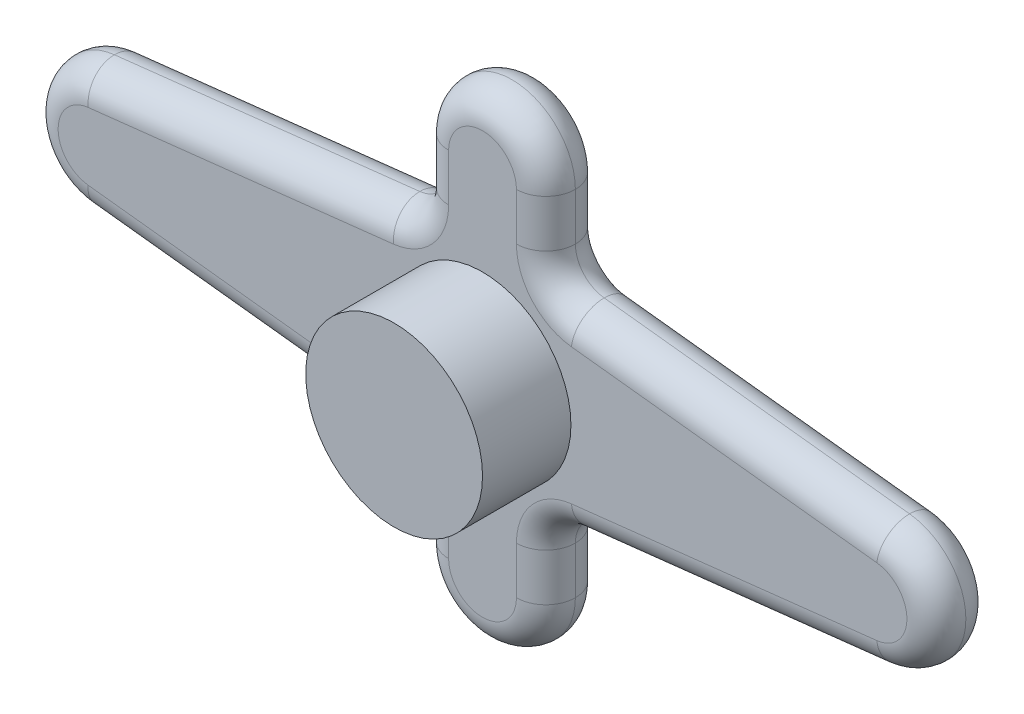
SolidWorks part; units mm, degrees
ref_plane "Front Plane" through (0, 0, 0) normal (0, 0, 1) x (1, 0, 0)
ref_plane "Top Plane" through (0, 0, 0) normal (0, 1, 0) x (1, 0, 0)
ref_plane "Right Plane" through (0, 0, 0) normal (1, 0, 0) x (0, 0, -1)
sketch "Sketch1" plane through (0, 0, 1307.6778) normal (0, 0, 1) x (1, 0, 0)
  line L16 (676.2339, 870.8041) -> (676.2339, 869.198)
  line L17 (680.5339, 869.198) -> (680.5339, 870.8041)
  line L18 (681.5111, 871.8972) -> (691.8739, 873.0615)
  line L19 (691.8739, 877.3346) -> (681.5111, 878.4989)
  line L20 (680.5339, 879.592) -> (680.5339, 881.198)
  line L21 (676.2339, 881.198) -> (676.2339, 879.592)
  line L22 (675.2567, 878.4989) -> (664.8938, 877.3346)
  line L23 (664.8938, 873.0615) -> (675.2567, 871.8972)
  line L24 (676.2339, 870.8041) -> (676.2339, 869.198)
  line L25 (680.5339, 869.198) -> (680.5339, 870.8041)
  line L26 (681.5111, 871.8972) -> (691.8739, 873.0615)
  line L27 (691.8739, 877.3346) -> (681.5111, 878.4989)
  line L28 (680.5339, 879.592) -> (680.5339, 881.198)
  line L29 (676.2339, 881.198) -> (676.2339, 879.592)
  line L30 (675.2567, 878.4989) -> (664.8938, 877.3346)
  line L31 (664.8938, 873.0615) -> (675.2567, 871.8972)
  arc A16 (676.2339, 870.8041) -> (675.2567, 871.8972) centre (675.1339, 870.8041) ccw
  arc A17 (676.2339, 869.198) -> (680.5339, 869.198) centre (678.3839, 869.198) ccw
  arc A18 (681.5111, 871.8972) -> (680.5339, 870.8041) centre (681.6339, 870.8041) ccw
  arc A19 (691.8739, 873.0615) -> (691.8739, 877.3346) centre (691.6339, 875.198) ccw
  arc A20 (680.5339, 879.592) -> (681.5111, 878.4989) centre (681.6339, 879.592) ccw
  arc A21 (680.5339, 881.198) -> (676.2339, 881.198) centre (678.3839, 881.198) ccw
  arc A22 (675.2567, 878.4989) -> (676.2339, 879.592) centre (675.1339, 879.592) ccw
  arc A23 (664.8938, 877.3346) -> (664.8938, 873.0615) centre (665.1339, 875.198) ccw
  arc A24 (676.2339, 870.8041) -> (675.2567, 871.8972) centre (675.1339, 870.8041) ccw
  arc A25 (676.2339, 869.198) -> (680.5339, 869.198) centre (678.3839, 869.198) ccw
  arc A26 (681.5111, 871.8972) -> (680.5339, 870.8041) centre (681.6339, 870.8041) ccw
  arc A27 (691.8739, 873.0615) -> (691.8739, 877.3346) centre (691.6339, 875.198) ccw
  arc A28 (680.5339, 879.592) -> (681.5111, 878.4989) centre (681.6339, 879.592) ccw
  arc A29 (680.5339, 881.198) -> (676.2339, 881.198) centre (678.3839, 881.198) ccw
  arc A30 (675.2567, 878.4989) -> (676.2339, 879.592) centre (675.1339, 879.592) ccw
  arc A31 (664.8938, 877.3346) -> (664.8938, 873.0615) centre (665.1339, 875.198) ccw
  dimension "D1" = 0.1
extrude "Boss-Extrude1" add sketch "Sketch1" along normal blind 2
sketch "Sketch2" plane through (0, 0, 1309.6778) normal (0, 0, 1) x (1, 0, 0)
  circle A0 centre (678.3839, 875.198) radius 3
extrude "Boss-Extrude2" add sketch "Sketch2" along normal blind 3
fillet "Fillet1" radius 1 32 edges at (675.954, 878.8589, 1307.6778) (676.2339, 880.395, 1307.6778) (678.3839, 883.348, 1307.6778) (680.5339, 880.395, 1307.6778) (680.8138, 878.8589, 1307.6778) (686.6925, 877.9167, 1307.6778) (693.7839, 875.198, 1307.6778) (686.6925, 872.4794, 1307.6778) (680.8138, 871.5372, 1307.6778) (680.5339, 870.0011, 1307.6778) (678.3839, 867.048, 1307.6778) (676.2339, 870.0011, 1307.6778) (675.954, 871.5372, 1307.6778) (670.0753, 872.4794, 1307.6778) (662.9839, 875.198, 1307.6778) (670.0753, 877.9167, 1307.6778) (675.954, 878.8589, 1309.6778) (676.2339, 880.395, 1309.6778) (678.3839, 883.348, 1309.6778) (680.5339, 880.395, 1309.6778) (680.8138, 878.8589, 1309.6778) (686.6925, 877.9167, 1309.6778) (693.7839, 875.198, 1309.6778) (686.6925, 872.4794, 1309.6778) (680.8138, 871.5372, 1309.6778) (680.5339, 870.0011, 1309.6778) (678.3839, 867.048, 1309.6778) (676.2339, 870.0011, 1309.6778) (675.954, 871.5372, 1309.6778) (670.0753, 872.4794, 1309.6778) (662.9839, 875.198, 1309.6778) (670.0753, 877.9167, 1309.6778)
